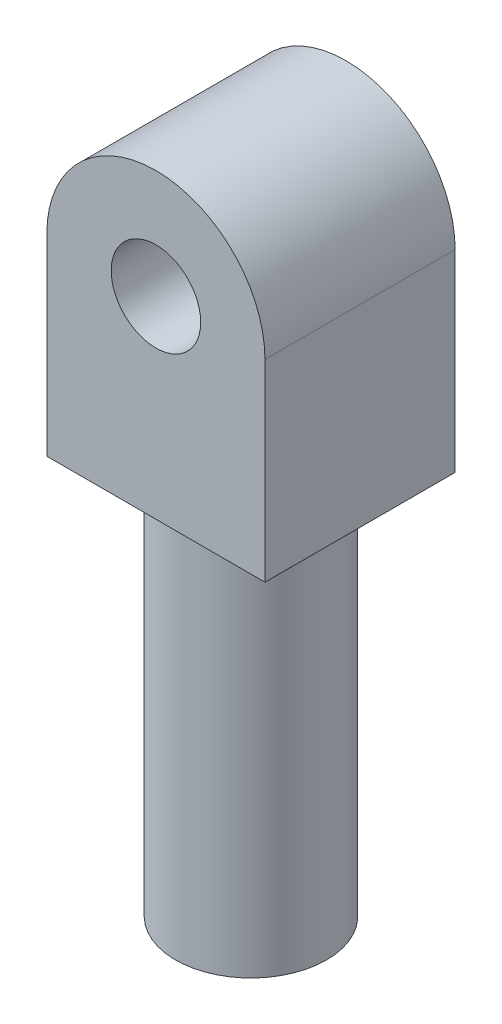
SolidWorks part; units mm, degrees
ref_plane "Front Plane" through (0, 0, 0) normal (0, 0, 1) x (1, 0, 0)
ref_plane "Top Plane" through (0, 0, 0) normal (0, 1, 0) x (1, 0, 0)
ref_plane "Right Plane" through (0, 0, 0) normal (1, 0, 0) x (0, 0, -1)
sketch "Sketch1" plane through (0, 0, 0) normal (0, 0, 1) x (1, 0, 0)
  line L2 (-9.75, 0) -> (-9.75, -17.25)
  line L3 (-9.75, -17.25) -> (9.75, -17.25)
  line L4 (9.75, 0) -> (9.75, -17.25)
  arc A0 (9.75, 0) -> (-9.75, 0) centre (0, 0) ccw
  circle A1 centre (0, 0) radius 4
  point P1 (0, 9.75)
  dimension "D1" = 19.5
  dimension "D2" = 27
  dimension "D3" = 8
extrude "Boss-Extrude2" add sketch "Sketch1" along normal blind 17
sketch "Sketch2" plane through (0, -17.25, 0) normal (0, -1, 0) x (1, 0, 0)
  line L0 (0, 0) -> (0, 17) construction
  line L1 (-9.75, 17) -> (9.75, 17) construction
  circle A0 centre (0, 8.5) radius 6.75
  dimension "D1" = 13.5
extrude "Boss-Extrude3" add sketch "Sketch2" along normal blind 35
